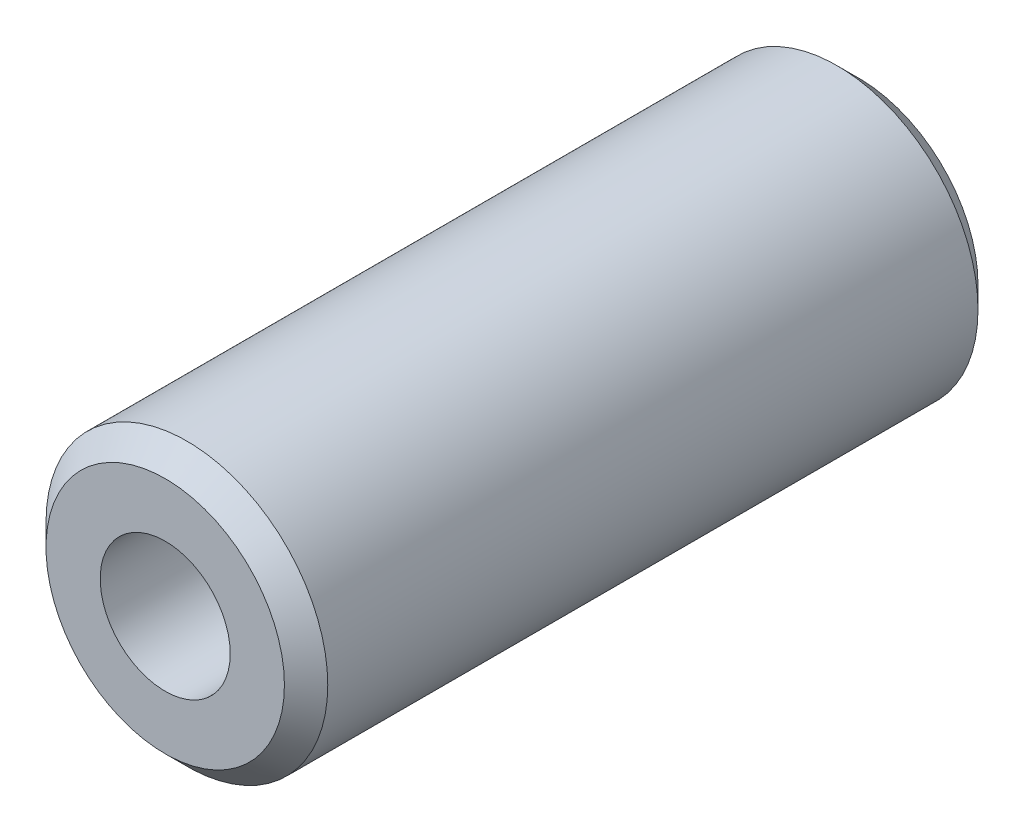
SolidWorks part; units mm, degrees
material "AISI 8620 Steel, carburized"
ref_plane "Front Plane" through (0, 0, 0) normal (1, 0, 0) x (0, 1, 0)
ref_plane "Top Plane" through (0, 0, 0) normal (0, 0, 1) x (0, 1, 0)
ref_plane "Right Plane" through (0, 0, 0) normal (0, 1, 0) x (-1, 0, 0)
sketch "Sketch1" plane through (0, 0, 0) normal (0, 0, 1) x (0, 1, 0)
  circle A0 centre (0, 0) radius 6.5
  circle A1 centre (0, 0) radius 3
  dimension "D1" = 13
  dimension "D2" = 6
extrude "Boss-Extrude1" add sketch "Sketch1" along normal blind 32
chamfer "Chamfer1" distance 1 angle 45 2 edges at (6.5, 0, 0) (6.5, 0, 32)
ref_axis "Axis1" through (0, 0, 35.0195) along (0, 0, -1)
